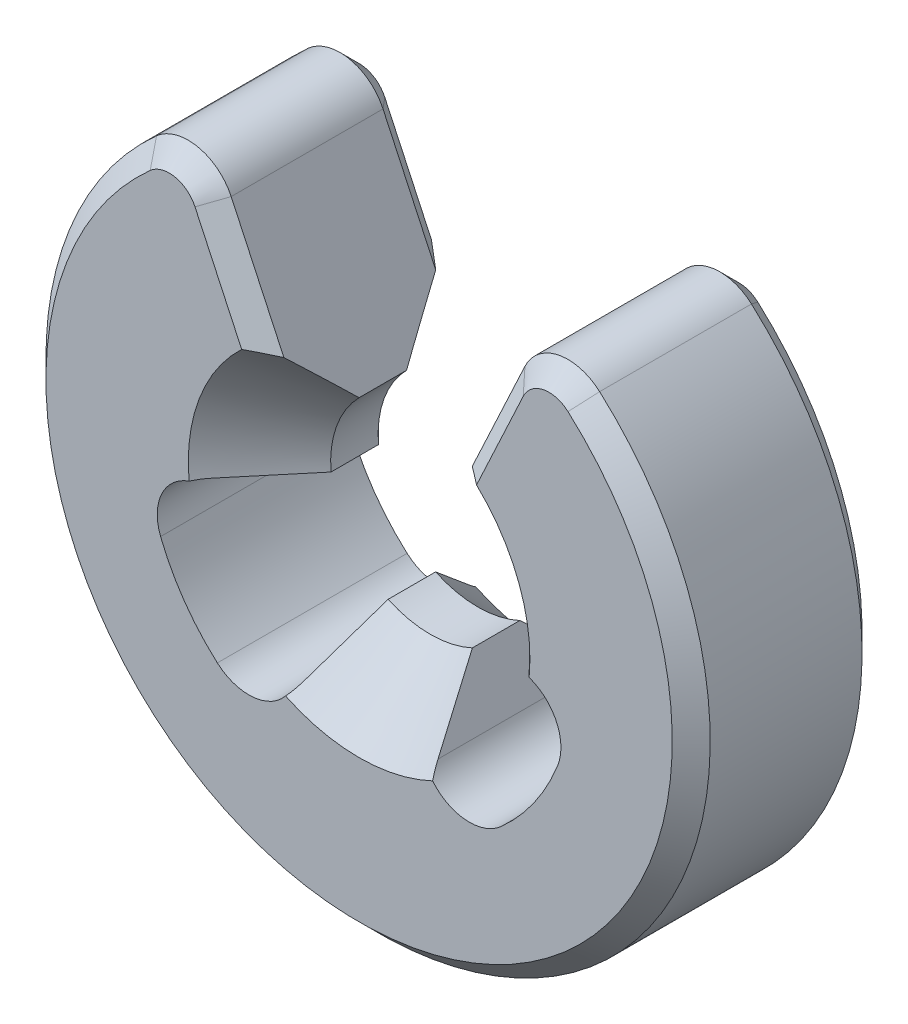
SolidWorks part; units mm, degrees
ref_plane "Front" through (0, 0, 0) normal (0, 0, 1) x (1, 0, 0)
ref_plane "Top" through (0, 0, 0) normal (0, 1, 0) x (1, 0, 0)
ref_plane "Right" through (0, 0, 0) normal (1, 0, 0) x (0, 0, -1)
sketch "Sketch1" plane through (0, 0, 0) normal (0, 0, 1) x (1, 0, 0)
  line L0 (0, 0) -> (0, 2.25) construction
  line L1 (1.2726, 1.8555) -> (1.8055, 2.9984)
  line L2 (-1.2726, 1.8555) -> (-1.8055, 2.9984)
  line L3 (0, 0) -> (2.25, 0) construction
  line L4 (2.25, 0) -> (3.5, 0) construction
  line L5 (1.2726, 1.8555) -> (0.75, 0.7348) construction
  line L6 (-1.2726, 1.8555) -> (-0.75, 0.7348) construction
  circle A0 centre (0, 0) radius 2.25 construction
  arc A1 (1.2726, 1.8555) -> (-1.2726, 1.8555) centre (0, 0) cw
  arc A2 (1.8055, 2.9984) -> (-1.8055, 2.9984) centre (0, 0) cw
  circle A3 centre (0, 0) radius 1.05 construction
  dimension "D1" = 4.5
  dimension "D2" = 3.5
  dimension "D4" = 2.1
  dimension "D3" = 1.5
  dimension "D5" = 50
extrude "Main Body" add sketch "Sketch1" along normal mid plane 2
sketch "Sketch2" plane through (0, 0, 0) normal (0, 0, 1) x (1, 0, 0)
  line L0 (1.2726, 1.8555) -> (0.75, 0.7348)
  line L2 (2.2414, -0.1961) -> (1.046, -0.0915)
  line L3 (1.2726, 1.8555) -> (0.75, 0.7348) construction
  line L4 (0, 0) -> (0, 2.25) construction
  line L5 (-2.2414, -0.1961) -> (-1.046, -0.0915)
  line L6 (-1.2726, 1.8555) -> (-0.75, 0.7348)
  line L7 (0.9509, -2.0392) -> (0.4437, -0.9516)
  line L8 (-0.9509, -2.0392) -> (-0.4437, -0.9516)
  line L9 (0, 0) -> (0, 2.25) construction
  arc A0 (-0.75, 0.7348) -> (-1.046, -0.0915) centre (0, 0) ccw
  arc A1 (-1.2726, 1.8555) -> (1.2726, 1.8555) centre (0, 0) ccw construction
  arc A2 (1.046, -0.0915) -> (0.75, 0.7348) centre (0, 0) ccw
  arc A3 (-0.4437, -0.9516) -> (0.4437, -0.9516) centre (0, 0) ccw
  circle A4 centre (0, 0) radius 2.25 construction
  arc A5 (2.2414, -0.1961) -> (1.2726, 1.8555) centre (0, 0) ccw
  arc A6 (-0.9509, -2.0392) -> (0.9509, -2.0392) centre (0, 0) ccw
  arc A7 (-1.2726, 1.8555) -> (-2.2414, -0.1961) centre (0, 0) ccw
  circle A10 centre (0, 0) radius 1.05 construction
  dimension "D2" = 85
  dimension "D3" = 25
extrude "Teeth" add sketch "Sketch2" along normal through all and the other way through all
chamfer "Chamfer1" distance 0.75 angle 45 6 edges at (-0.9885, 0.3541, 1) (-0.9885, 0.3541, -1) (0, -1.05, 1) (0, -1.05, -1) (0.9885, 0.3541, 1) (0.9885, 0.3541, -1)
fillet "Fillet1" radius 0.5 6 edges at (2.2414, -0.1961, 0) (0.9509, -2.0392, 0) (-0.9509, -2.0392, 0) (-2.2414, -0.1961, 0) (1.8055, 2.9984, 0) (-1.8055, 2.9984, 0)
chamfer "Deburs" distance 0.2 angle 45 10 edges at (-1.3136, 1.9435, 1) (1.3136, 1.9435, 1) (-1.9009, 2.7248, 1) (1.9009, 2.7248, 1) (0, -3.5, 1) (-1.3136, 1.9435, -1) (1.3136, 1.9435, -1) (-1.9009, 2.7248, -1) (1.9009, 2.7248, -1) (0, -3.5, -1)
